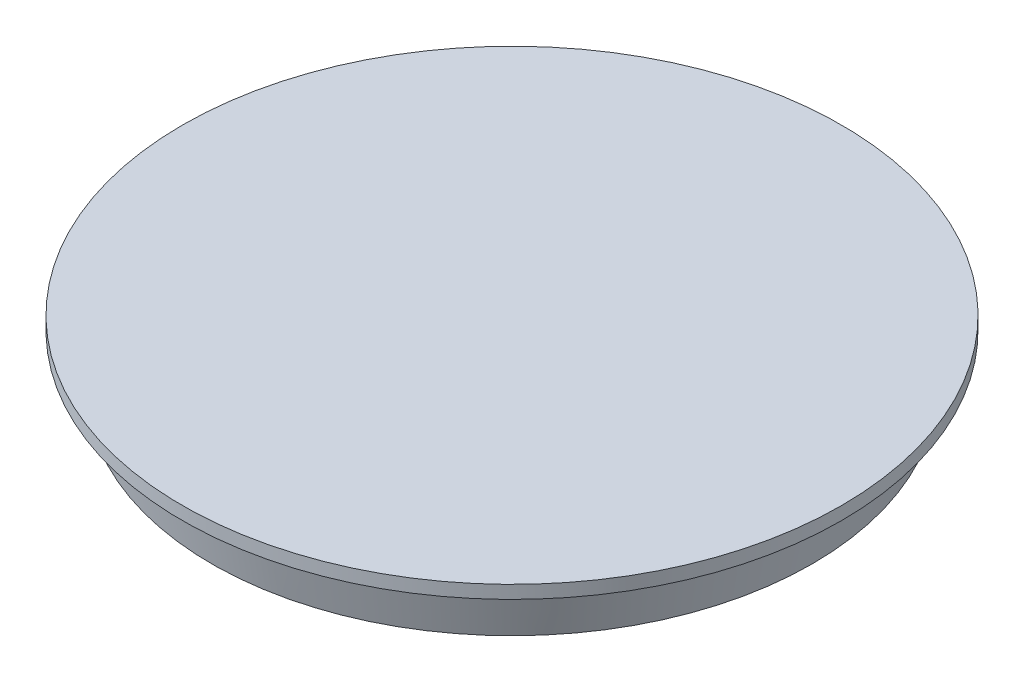
SolidWorks part; units mm, degrees
ref_plane "Front Plane" through (0, 0, 0) normal (0, 0, 1) x (1, 0, 0)
ref_plane "Top Plane" through (0, 0, 0) normal (0, 1, 0) x (1, 0, 0)
ref_plane "Right Plane" through (0, 0, 0) normal (1, 0, 0) x (0, 0, -1)
sketch "Sketch2" plane through (0, 0, 0) normal (0, 0, 1) x (1, 0, 0)
  line L1 (-25.25, 0) -> (-25.25, -1) construction
  line L2 (-25.25, -1) -> (-23.75, -1) construction
  line L3 (-23.75, -1) -> (-23, -5) construction
  line L4 (-23, -5) -> (-22, -5) construction
  line L5 (-22, -5) -> (-22, -1) construction
  line L7 (0, -2.75) -> (0, 2.75) construction
  line L8 (22, -5) -> (22, -1)
  line L9 (23, -5) -> (22, -5)
  line L10 (23.75, -1) -> (23, -5)
  line L11 (25.25, -1) -> (23.75, -1)
  line L12 (25.25, 0) -> (25.25, -1)
  line L13 (0, 0) -> (0, -1) construction
  line L14 (-25.25, 0) -> (0, 0) construction
  line L15 (0, 0) -> (25.25, 0)
  line L16 (-22, -1) -> (0, -1) construction
  line L17 (0, -1) -> (22, -1)
  line L18 (0, -1) -> (0, 0)
  point P17 (0, 0)
  dimension "D1" = 50.5
  dimension "D2" = 46
  dimension "D3" = 47.5
  dimension "D4" = 1
  dimension "D5" = 1
  dimension "D6" = 4
revolve "Revolve3" add sketch "Sketch2" angle 360 about L18
fillet "Fillet1" radius 4 1 edges at (22, -1, 0)
